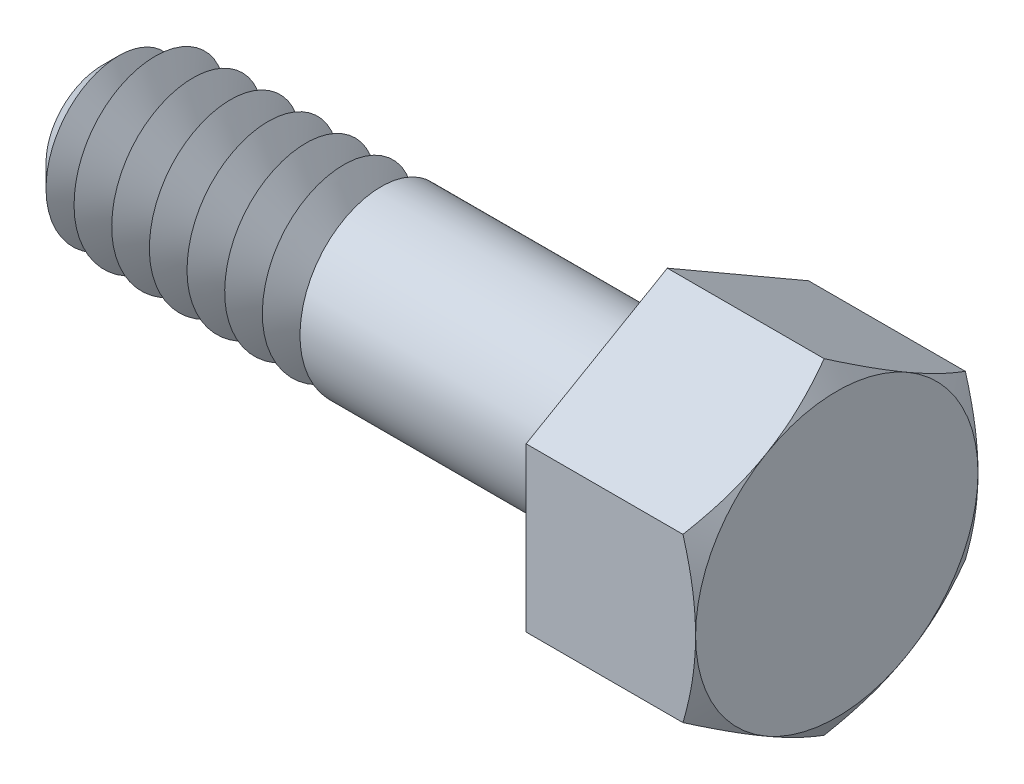
SolidWorks part; units mm, degrees
ref_plane "Front Plane" through (0, 0, 0) normal (0, 0, 1) x (1, 0, 0)
ref_plane "Top Plane" through (0, 0, 0) normal (0, 1, 0) x (1, 0, 0)
ref_plane "Right Plane" through (0, 0, 0) normal (1, 0, 0) x (0, 0, -1)
sketch "Sketch2" plane through (0, 0, 0) normal (1, 0, 0) x (0, 0, -1)
  line L1 (0, -2.8868) -> (2.5, -1.4434)
  line L2 (2.5, -1.4434) -> (2.5, 1.4434)
  line L3 (2.5, 1.4434) -> (0, 2.8868)
  line L4 (0, 2.8868) -> (-2.5, 1.4434)
  line L5 (-2.5, 1.4434) -> (-2.5, -1.4434)
  line L6 (-2.5, -1.4434) -> (0, -2.8868)
  circle A0 centre (0, 0) radius 2.5 construction
  dimension "D1" = 5
extrude "Boss-Extrude1" add sketch "Sketch2" along normal blind 3
sketch "Sketch3" plane through (3, 0, 0) normal (1, 0, 0) x (0, 0, -1)
  circle A0 centre (0, 0) radius 2.5
extrude "Cut-Extrude1" cut sketch "Sketch3" against normal blind 3 draft 60 flip side to cut
sketch "Sketch4" plane through (0, 0, 0) normal (-1, 0, 0) x (0, 0, 1)
  circle A0 centre (0, 0) radius 1.5
extrude "Boss-Extrude2" add sketch "Sketch4" along normal blind 10
chamfer "Chamfer1" distance 0.5 angle 45 1 edges at (-10, 0, 1.5)
sketch "Sketch5" plane through (-10, 0, 0) normal (-1, 0, 0) x (0, 0, 1)
  circle A0 centre (0, 0) radius 1.5
curve "Helix/Spiral1" pitch 0.6667 height 5 radius 1.5 centre (-10, 0, 0) axis (1, 0, 0) start towards (0, 0, 1)
sketch "Sketch6" plane through (0, 0, 0) normal (0, 1, 0) x (1, 0, 0)
  line L1 (-10, -0.9226) -> (-10.5, -1.7887)
  line L2 (-10.5, -1.7887) -> (-9.5, -1.7887)
  line L3 (-9.5, -1.7887) -> (-10, -0.9226)
  circle A0 centre (-10, -1.5) radius 0.2887 construction
  spline S0 degree 3 poles (-10, -1.5) (-9.9862, -1.5) (-9.9583, -1.4219) (-9.9167, -1.0883) (-9.875, -0.589) (-9.8333, 0) (-9.7917, 0.589) (-9.75, 1.0883) (-9.7083, 1.4219) (-9.6667, 1.5391) (-9.625, 1.4219) (-9.5833, 1.0883) (-9.5417, 0.589) (-9.5, 0) (-9.4583, -0.589) (-9.4167, -1.0883) (-9.375, -1.4219) (-9.3333, -1.5391) (-9.2917, -1.4219) (-9.25, -1.0883) (-9.2083, -0.589) (-9.1667, 0) (-9.125, 0.589) (-9.0833, 1.0883) (-9.0417, 1.4219) (-9, 1.5391) (-8.9583, 1.4219) (-8.9167, 1.0883) (-8.875, 0.589) (-8.8333, 0) (-8.7917, -0.589) (-8.75, -1.0883) (-8.7083, -1.4219) (-8.6667, -1.5391) (-8.625, -1.4219) (-8.5833, -1.0883) (-8.5417, -0.589) (-8.5, 0) (-8.4583, 0.589) (-8.4167, 1.0883) (-8.375, 1.4219) (-8.3333, 1.5391) (-8.2917, 1.4219) (-8.25, 1.0883) (-8.2083, 0.589) (-8.1667, 0) (-8.125, -0.589) (-8.0833, -1.0883) (-8.0417, -1.4219) (-8, -1.5391) (-7.9583, -1.4219) (-7.9167, -1.0883) (-7.875, -0.589) (-7.8333, 0) (-7.7917, 0.589) (-7.75, 1.0883) (-7.7083, 1.4219) (-7.6667, 1.5391) (-7.625, 1.4219) (-7.5833, 1.0883) (-7.5417, 0.589) (-7.5, 0) (-7.4583, -0.589) (-7.4167, -1.0883) (-7.375, -1.4219) (-7.3333, -1.5391) (-7.2917, -1.4219) (-7.25, -1.0883) (-7.2083, -0.589) (-7.1667, 0) (-7.125, 0.589) (-7.0833, 1.0883) (-7.0417, 1.4219) (-7, 1.5391) (-6.9583, 1.4219) (-6.9167, 1.0883) (-6.875, 0.589) (-6.8333, 0) (-6.7917, -0.589) (-6.75, -1.0883) (-6.7083, -1.4219) (-6.6667, -1.5391) (-6.625, -1.4219) (-6.5833, -1.0883) (-6.5417, -0.589) (-6.5, 0) (-6.4583, 0.589) (-6.4167, 1.0883) (-6.375, 1.4219) (-6.3333, 1.5391) (-6.2917, 1.4219) (-6.25, 1.0883) (-6.2083, 0.589) (-6.1667, 0) (-6.125, -0.589) (-6.0833, -1.0883) (-6.0417, -1.4219) (-6, -1.5391) (-5.9583, -1.4219) (-5.9167, -1.0883) (-5.875, -0.589) (-5.8333, 0) (-5.7917, 0.589) (-5.75, 1.0883) (-5.7083, 1.4219) (-5.6667, 1.5391) (-5.625, 1.4219) (-5.5833, 1.0883) (-5.5417, 0.589) (-5.5, 0) (-5.4583, -0.589) (-5.4167, -1.0883) (-5.375, -1.4219) (-5.3333, -1.5391) (-5.2917, -1.4219) (-5.25, -1.0883) (-5.2083, -0.589) (-5.1667, 0) (-5.125, 0.589) (-5.0833, 1.0883) (-5.0417, 1.4219) (-5.0138, 1.5) (-5, 1.5) knots 0 0 0 0 0.008333 0.016667 0.025 0.033333 0.041667 0.05 0.058333 0.066667 0.075 0.083333 0.091667 0.1 0.108333 0.116667 0.125 0.133333 0.141667 0.15 0.158333 0.166667 0.175 0.183333 0.191667 0.2 0.208333 0.216667 0.225 0.233333 0.241667 0.25 0.258333 0.266667 0.275 0.283333 0.291667 0.3 0.308333 0.316667 0.325 0.333333 0.341667 0.35 0.358333 0.366667 0.375 0.383333 0.391667 0.4 0.408333 0.416667 0.425 0.433333 0.441667 0.45 0.458333 0.466667 0.475 0.483333 0.491667 0.5 0.508333 0.516667 0.525 0.533333 0.541667 0.55 0.558333 0.566667 0.575 0.583333 0.591667 0.6 0.608333 0.616667 0.625 0.633333 0.641667 0.65 0.658333 0.666667 0.675 0.683333 0.691667 0.7 0.708333 0.716667 0.725 0.733333 0.741667 0.75 0.758333 0.766667 0.775 0.783333 0.791667 0.8 0.808333 0.816667 0.825 0.833333 0.841667 0.85 0.858333 0.866667 0.875 0.883333 0.891667 0.9 0.908333 0.916667 0.925 0.933333 0.941667 0.95 0.958333 0.966667 0.975 0.983333 0.991667 1 1 1 1 construction
sweep "Cut-Sweep1" cut profiles "Sketch6" path "Helix/Spiral1"
